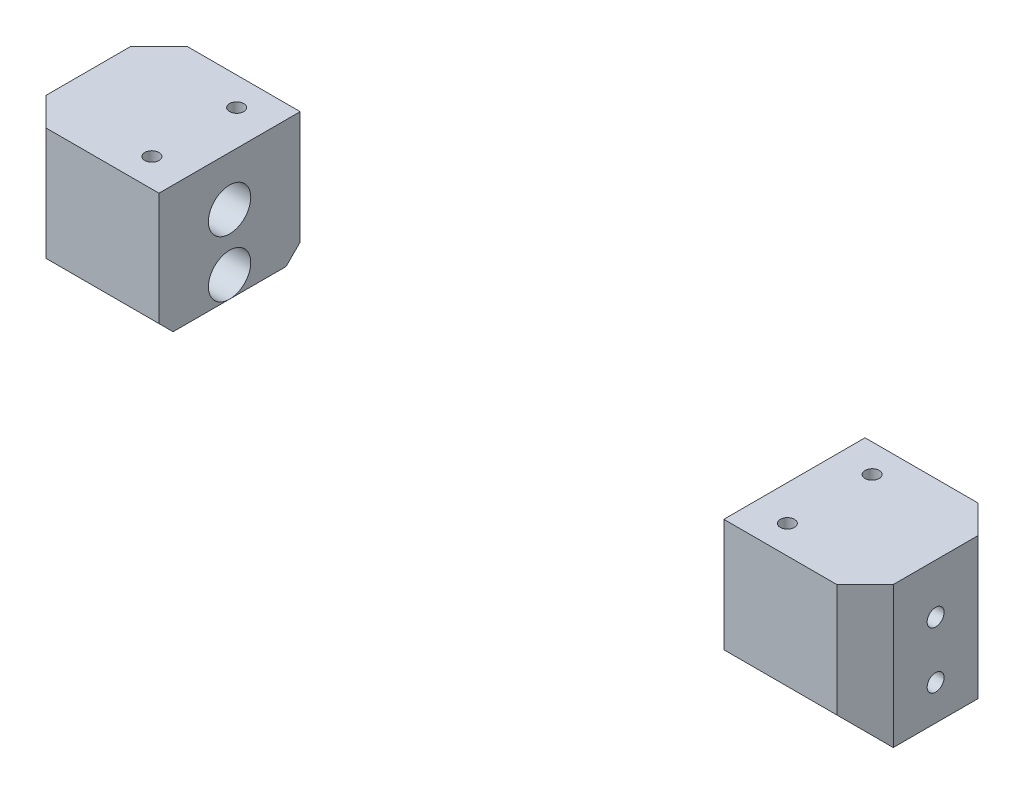
SolidWorks part; units mm, degrees
ref_plane "Front" through (0, 0, 0) normal (0, 0, 1) x (1, 0, 0)
ref_plane "Top" through (0, 0, 0) normal (0, 1, 0) x (1, 0, 0)
ref_plane "Right" through (0, 0, 0) normal (1, 0, 0) x (0, 0, -1)
sketch "草图1" plane through (0, 0, 0) normal (0, 1, 0) x (1, 0, 0)
  line L1 (30, -5) -> (-30, -5)
  line L2 (30, -5) -> (30, 5)
  line L3 (30, 5) -> (-30, 5)
  line L4 (-30, -5) -> (-30, 5)
  line L5 (30, -5) -> (-30, 5) construction
  line L6 (30, 5) -> (-30, -5) construction
  point P0 (0, 0)
  dimension "D1" = 10
  dimension "D2" = 60
extrude "凸台-拉伸1" add sketch "草图1" along normal blind 10
sketch "草图2" plane through (-30, 0, 0) normal (-1, 0, 0) x (0, 0, 1)
  line L0 (0, 14.8135) -> (0, -3.8643) construction
  line L1 (-5, 0) -> (5, 0) construction
  circle A0 centre (0, 6.5) radius 0.6
  circle A1 centre (0, 2.5) radius 0.6
  dimension "D1" = 1.2
  dimension "D2" = 1.2
  dimension "D3" = 4
  dimension "D4" = 2.5
extrude "切除-拉伸1" cut sketch "草图2" against normal through all
sketch "草图4" plane through (0, 0, 0) normal (0, -1, 0) x (1, 0, 0)
  line L0 (-30, 5) -> (30, 5) construction
  line L1 (11, -5) -> (-11, -5)
  line L2 (11, -5) -> (11, 5)
  line L3 (11, 5) -> (-11, 5)
  line L4 (-11, -5) -> (-11, 5)
  line L5 (11, -5) -> (-11, 5) construction
  line L6 (11, 5) -> (-11, -5) construction
  point P0 (0, 0)
  dimension "D1" = 22
sketch "草图5" plane through (0, 10, 0) normal (0, 1, 0) x (1, 0, 0)
  line L0 (-43.3222, 0) -> (41.3531, 0) construction
  line L1 (0, 23.1146) -> (0, -15.7067) construction
  line L3 (-22.5, 20.8095) -> (-22.5, -18.1592) construction
  circle A4 centre (-22.5, 3) radius 0.5
  circle A5 centre (-22.5, -3) radius 0.5
  circle A6 centre (22.5, -3) radius 0.5
  circle A7 centre (22.5, 3) radius 0.5
  dimension "D1" = 45
  dimension "D2" = 1
  dimension "D3" = 6
extrude "切除-拉伸3" cut sketch "草图5" against normal through all
chamfer "倒角2" distance 2 angle 45 2 edges at (0, 0, -5) (0, 0, 5)
chamfer "倒角3" distance 2 angle 45 4 edges at (-30, 6, -5) (-30, 6, 5) (30, 6, 5) (30, 6, -5)
sketch "草图6" plane through (0, 10, 0) normal (0, 1, 0) x (1, 0, 0)
  line L0 (28, 5) -> (-28, 5) construction
  line L1 (20, -5) -> (-20, -5)
  line L2 (20, -5) -> (20, 5)
  line L3 (20, 5) -> (-20, 5)
  line L4 (-20, -5) -> (-20, 5)
  line L5 (20, -5) -> (-20, 5) construction
  line L6 (20, 5) -> (-20, -5) construction
  point P0 (0, 0)
  dimension "D1" = 40
extrude "切除-拉伸4" cut sketch "草图6" against normal through all
extrude "切除-拉伸5" [suppressed] cut sketch "草图4" against normal blind 3
chamfer "倒角4" [suppressed] distance 3 angle 45
chamfer "倒角5" [suppressed] distance 1 angle 45
chamfer "倒角6" distance 1 angle 45 1 edges at (-20, 0, 0)
chamfer "倒角7" distance 1 angle 30 1 edges at (20, 0, 0) first distance on face at (20, 6.5, -0.6)
ref_plane "基准面1" through (0, 0, 0) normal (1, 0, 0) x (0, 0, -1)
sketch "草图7" plane through (-20, 0, 0) normal (1, 0, 0) x (0, 0, -1)
  circle A0 centre (0, 6.5) radius 1.5
  circle A1 centre (0, 2.5) radius 1.5
  dimension "D1" = 3
  dimension "D2" = 3
extrude "切除-拉伸6" cut sketch "草图7" against normal offset from surface (5 mm away) 5 up to face at (-30, 6.5, 0.6)
sketch "草图8" plane through (20, 0, 0) normal (1, 0, 0) x (0, 0, -1)
  circle A0 centre (0, 6.5) radius 1.5
  circle A1 centre (0, 2.5) radius 1.5
  dimension "D1" = 3
  dimension "D2" = 3
extrude "切除-拉伸9" cut sketch "草图8" along normal offset from surface (5 mm away) 5 up to face at (30, 6.5, 0.6)
